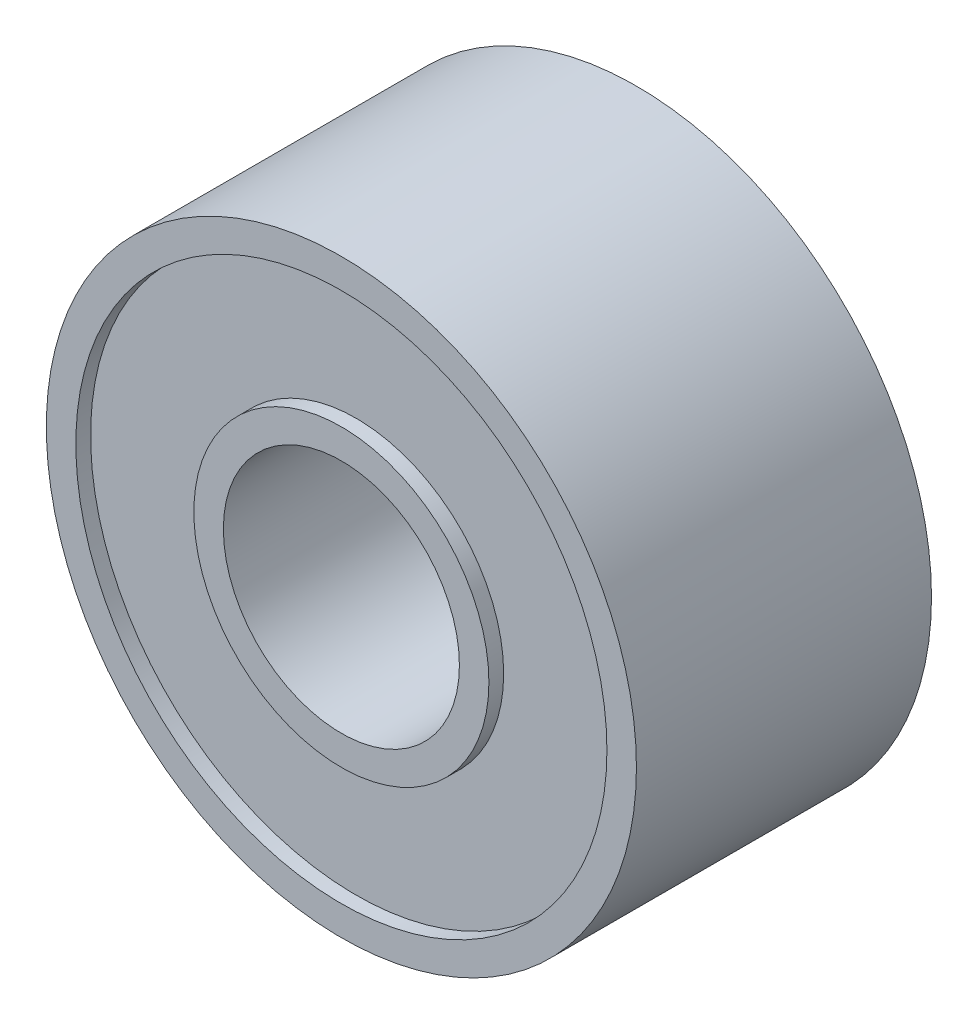
SolidWorks part; units mm, degrees
material "镀铬不锈钢"
ref_plane "前视基准面" through (0, 0, 0) normal (0, 0, 1) x (1, 0, 0)
ref_plane "上视基准面" through (0, 0, 0) normal (0, 1, 0) x (1, 0, 0)
ref_plane "右视基准面" through (0, 0, 0) normal (1, 0, 0) x (0, 0, -1)
sketch "草图1" plane through (0, 0, 0) normal (0, 0, 1) x (1, 0, 0)
  circle A0 centre (0, 0) radius 4
  circle A1 centre (0, 0) radius 10
  circle A2 centre (0, 0) radius 16
  circle A3 centre (0, 0) radius 5
  circle A4 centre (0, 0) radius 9
  dimension "D1" = 20
  dimension "D2" = 8
  dimension "D3" = 10
  dimension "D4" = 18
  dimension "D5" = 32
extrude "凸台-拉伸1" add sketch "草图1" along normal mid plane 9 contours A4 A3 region at (-8.7454, 0, 0)
extrude "凸台-拉伸2" add sketch "草图1<3>" along normal mid plane 10 contours A3 A0 | A1 A4 region at (-9.7172, 0, 0) region at (-4.8586, 0, 0)
sketch "草图1<3>" plane through (0, 0, 0) normal (0, 0, 1) x (1, 0, 0) same geometry as "草图1"
